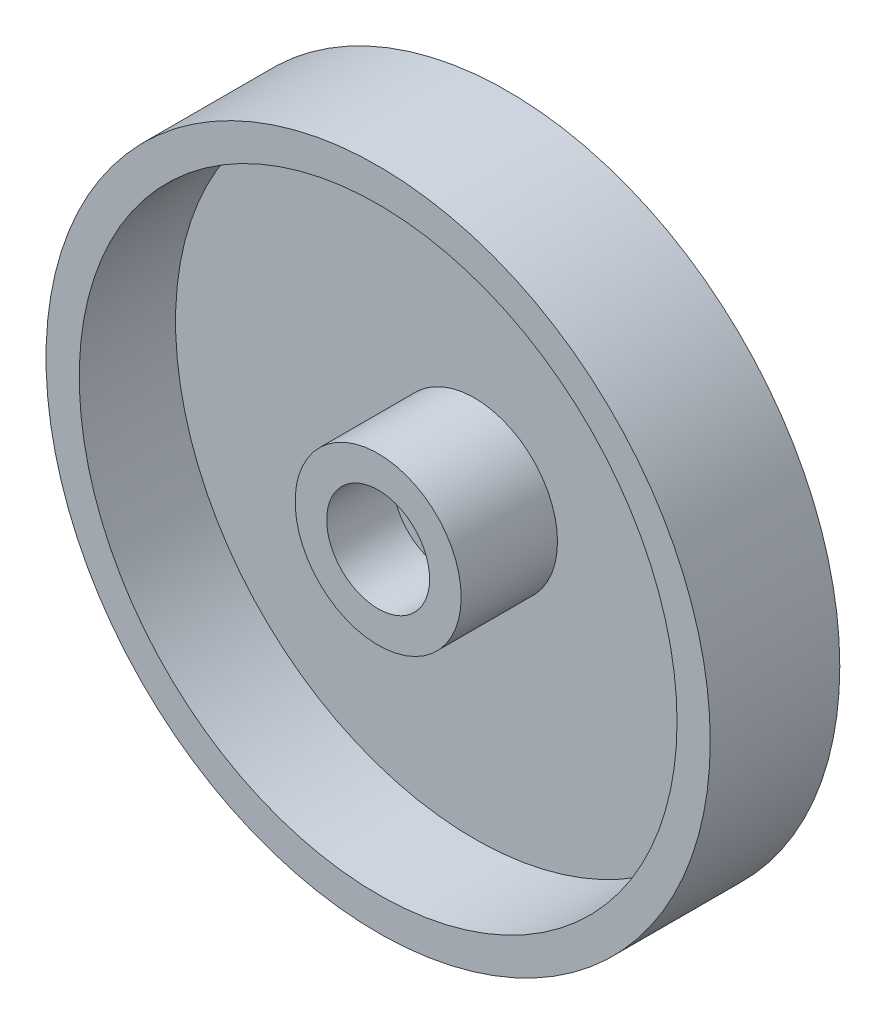
SolidWorks part; units mm, degrees
ref_plane "前视基准面" through (0, 0, 0) normal (0, 0, 1) x (1, 0, 0)
ref_plane "上视基准面" through (0, 0, 0) normal (0, 1, 0) x (1, 0, 0)
ref_plane "右视基准面" through (0, 0, 0) normal (1, 0, 0) x (0, 0, -1)
sketch "草图1" plane through (0, 0, 0) normal (0, 0, 1) x (1, 0, 0)
  circle A0 centre (0, 0) radius 5
  circle A1 centre (0, 0) radius 3.1
  circle A2 centre (0, 0) radius 18
  circle A3 centre (0, 0) radius 20
  dimension "D1" = 40
  dimension "D2" = 36
  dimension "D3" = 6.2
  dimension "D4" = 10
extrude "凸台-拉伸1" add sketch "草图1" along normal blind 4 contours A0 A1 region at (-4.8586, 0, 0)
extrude "凸台-拉伸2" add sketch "草图1<3>" along normal blind 4 separate body contours A3 A2 region at (-19.4343, 0, 0)
sketch "草图1<3>" plane through (0, 0, 0) normal (0, 0, 1) x (1, 0, 0) same geometry as "草图1"
extrude "凸台-拉伸3" add sketch "草图1<4>" against normal blind 2 contours A2 A0 | A1 | A0 A1 | A3 A2 region at (-4.8586, 0, 0) region at (0, 0, 0) region at (-17.4909, 0, 0) region at (-19.4343, 0, 0)
sketch "草图1<4>" plane through (0, 0, 0) normal (0, 0, 1) x (1, 0, 0) same geometry as "草图1"
sketch "草图2" plane through (0, 0, -2) normal (0, 0, -1) x (-1, 0, 0)
  circle A0 centre (0, 0) radius 20
extrude "凸台-拉伸4" add sketch "草图2" along normal blind 1.8
sketch "草图4" plane through (0, 0, 0) normal (0, 0, 1) x (1, 0, 0)
  circle A0 centre (0, 0) radius 5
  circle A1 centre (0, 0) radius 18
extrude "切除-拉伸1" cut sketch "草图4" against normal blind 1.8 contours A0 | A1
